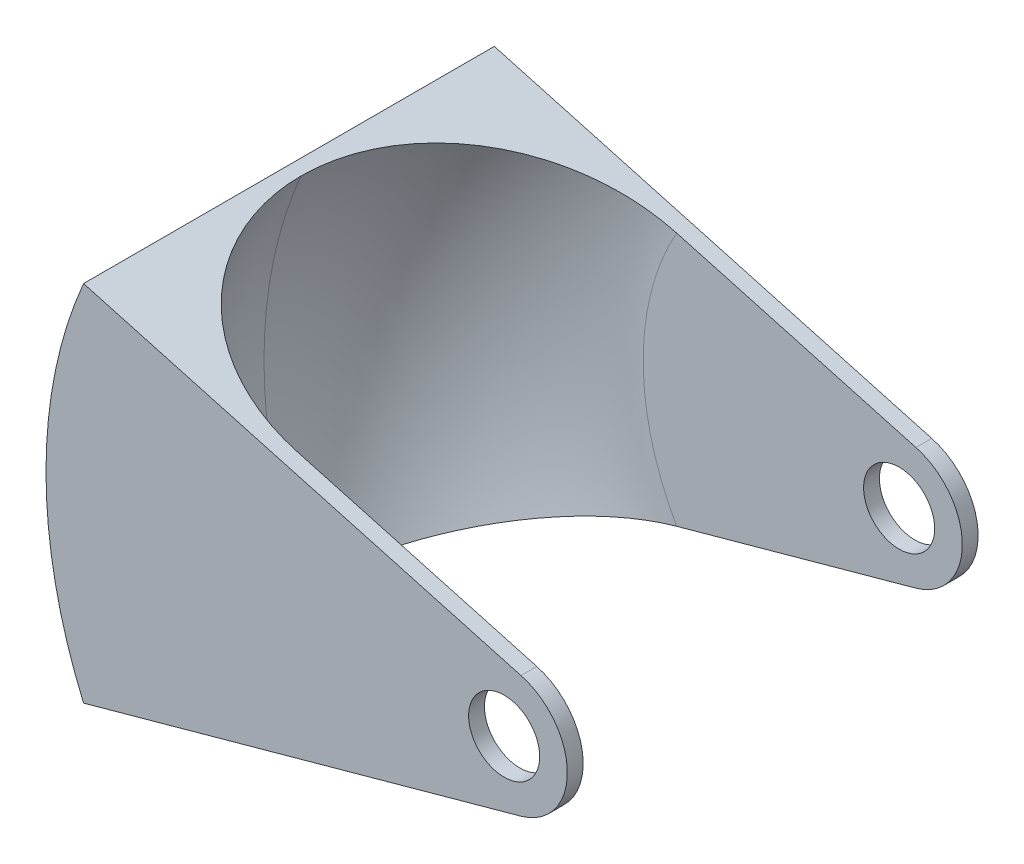
SolidWorks part; units mm, degrees
ref_plane "Front Plane" through (0, 0, 0) normal (0, 0, 1) x (1, 0, 0)
ref_plane "Top Plane" through (0, 0, 0) normal (0, 1, 0) x (1, 0, 0)
ref_plane "Right Plane" through (0, 0, 0) normal (1, 0, 0) x (0, 0, -1)
sketch "Sketch1" plane through (0, 0, 0) normal (0, 0, 1) x (1, 0, 0)
  line L0 (6.7599, 24.4839) -> (-169.052, 73.025)
  line L1 (-169.052, -73.025) -> (6.7599, -24.4839)
  circle A0 centre (0, 0) radius 14.2875
  arc A2 (6.7599, -24.4839) -> (6.7599, 24.4839) centre (0, 0) ccw
  arc A3 (-169.052, 73.025) -> (-169.052, -73.025) centre (0, 0) ccw
  point P12 (-184.15, 0)
  dimension "D1" = 28.575
  dimension "D4" = 25.4
  dimension "D2" = 146.05
  dimension "D3" = 184.15
extrude "Boss-Extrude1" add sketch "Sketch1" against normal blind 165.1
sketch "Sketch2" plane through (0, 0, 0) normal (0, 1, 0) x (1, 0, 0)
  line L0 (-184.15, 165.1) -> (-184.15, 0) construction
  line L1 (-184.15, 158.75) -> (25.4, 158.75)
  line L2 (-184.15, 158.75) -> (-184.15, 6.35)
  line L3 (-184.15, 6.35) -> (25.4, 6.35)
  line L4 (25.4, 158.75) -> (25.4, 6.35)
  line L5 (25.4, 0) -> (25.4, 165.1) construction
  line L6 (6.7599, 0) -> (-169.052, 0) construction
  dimension "D1" = 152.4
  dimension "D2" = 6.35
extrude "Cut-Extrude1" cut sketch "Sketch2" against normal through all both and the other way through all
sketch "Sketch3" plane through (0, 0, -158.75) normal (0, 0, 1) x (1, 0, 0)
  line L0 (-169.052, 73.025) -> (-164.1552, 71.673)
  line L2 (-164.1552, -71.673) -> (-169.052, -73.025)
  line L3 (-169.052, -73.025) -> (6.7599, -24.4839) construction
  line L4 (6.7599, 24.4839) -> (-169.052, 73.025) construction
  arc A0 (-169.052, 73.025) -> (-169.052, -73.025) centre (0, 0) ccw
  arc A1 (-164.1552, 71.673) -> (-164.1552, -71.673) centre (0.5995, 0) ccw
  arc A2 (-169.052, 73.025) -> (-169.052, -73.025) centre (0, 0) ccw construction
  point P13 (-184.15, 0)
  point P14 (-179.07, 0)
  dimension "D1" = 5.08
  dimension "D2" = 5.08
  dimension "D3" = 5.08
extrude "Boss-Extrude2" add sketch "Sketch3" along normal up to next (152.4 mm away)
fillet "Fillet2" radius 76.2 2 edges at (-179.07, 0, -6.35) (-179.07, 0, -158.75)
